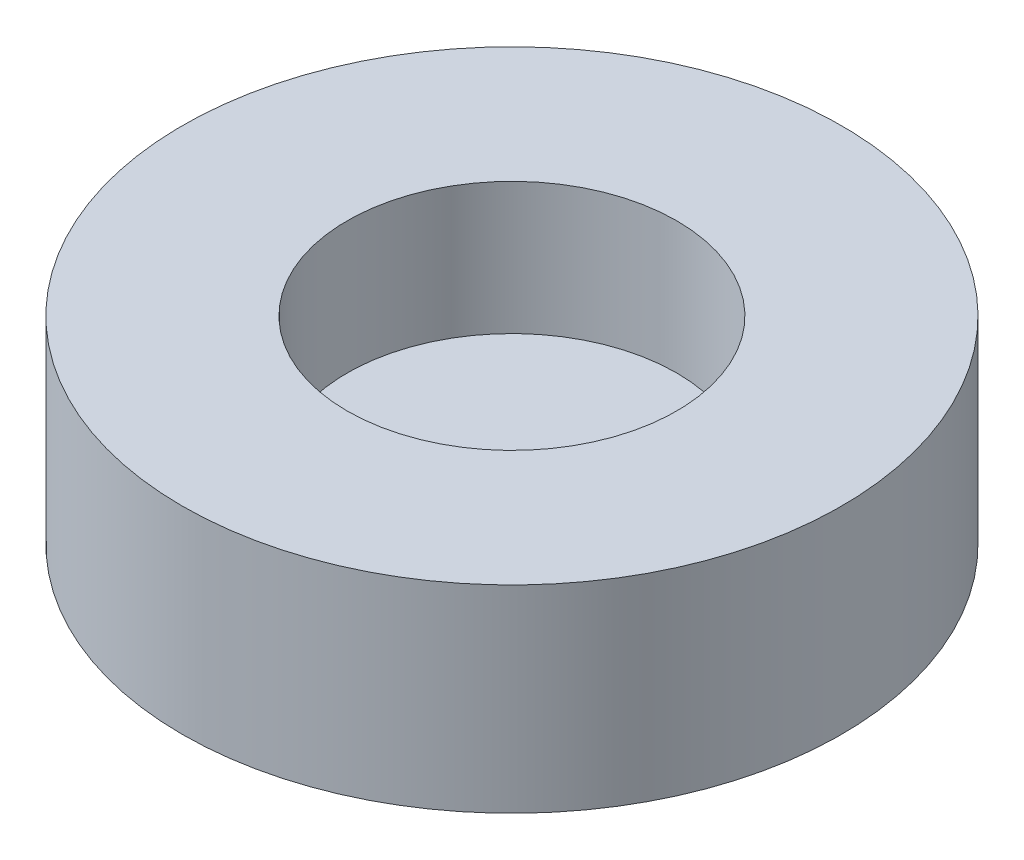
SolidWorks part; units mm, degrees
ref_plane "Front Plane" through (0, 0, 0) normal (0, 0, 1) x (1, 0, 0)
ref_plane "Top Plane" through (0, 0, 0) normal (0, 1, 0) x (1, 0, 0)
ref_plane "Right Plane" through (0, 0, 0) normal (1, 0, 0) x (0, 0, -1)
sketch "Sketch1" plane through (0, 0, 0) normal (0, 1, 0) x (1, 0, 0)
  circle A0 centre (0, 0) radius 10
  dimension "D1" = 20
extrude "Boss-Extrude2" add sketch "Sketch1" along normal blind 6
sketch "Sketch3" plane through (0, 6, 0) normal (0, 1, 0) x (1, 0, 0)
  circle A0 centre (0, 0) radius 5
  dimension "D1" = 10
extrude "Cut-Extrude1" cut sketch "Sketch3" against normal blind 4
